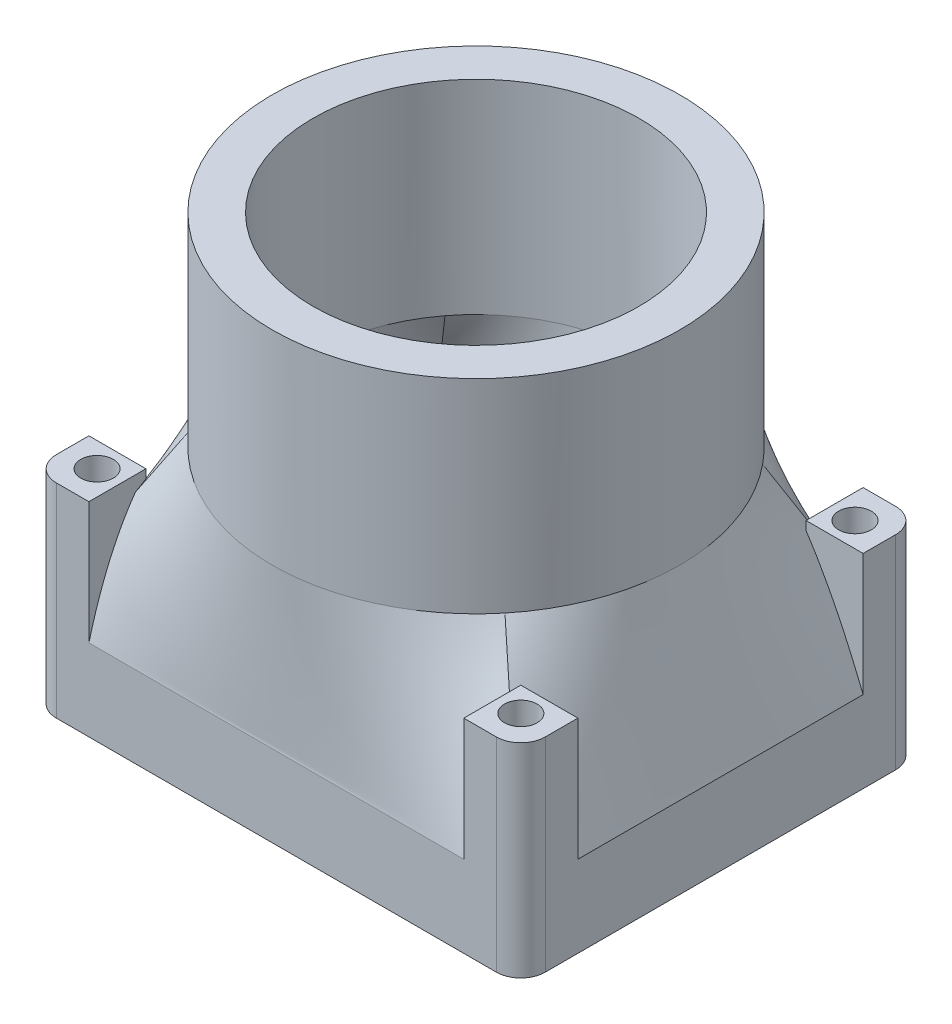
SolidWorks part; units mm, degrees
ref_plane "Front Plane" through (0, 0, 0) normal (0, 0, 1) x (1, 0, 0)
ref_plane "Top Plane" through (0, 0, 0) normal (0, 1, 0) x (1, 0, 0)
ref_plane "Right Plane" through (0, 0, 0) normal (1, 0, 0) x (0, 0, -1)
sketch "Sketch1" plane through (0, 0, 0) normal (0, 1, 0) x (1, 0, 0)
  line L0 (0, 24.5) -> (0, -24.5) construction
  line L1 (-30, -24.5) -> (30, -24.5)
  line L2 (-30, -24.5) -> (-30, 24.5)
  line L3 (-30, 24.5) -> (30, 24.5)
  line L4 (30, -24.5) -> (30, 24.5)
  line L5 (-30, -24.5) -> (30, 24.5) construction
  line L6 (-30, 24.5) -> (30, -24.5) construction
  line L7 (-30, 0) -> (30, 0) construction
  line L9 (-23, -17.5) -> (23, -17.5)
  line L10 (-23, -17.5) -> (-23, 17.5)
  line L11 (-23, 17.5) -> (23, 17.5)
  line L12 (23, -17.5) -> (23, 17.5)
  line L13 (-23, -17.5) -> (23, 17.5) construction
  line L14 (-23, 17.5) -> (23, -17.5) construction
  circle A0 centre (-26, 20.5) radius 2
  circle A1 centre (26, 20.5) radius 2
  circle A2 centre (26, -20.5) radius 2
  circle A3 centre (-26, -20.5) radius 2
  point P0 (0, 0)
  point P18 (0, 0)
  dimension "D1" = 4
  dimension "D2" = 4
  dimension "D3" = 4
  dimension "D4" = 60
  dimension "D5" = 49
  dimension "D6" = 35
  dimension "D7" = 46
extrude "Boss-Extrude1" add sketch "Sketch1" along normal blind 10
sketch "Sketch2" plane through (0, 10, 0) normal (0, 1, 0) x (1, 0, 0)
  line L1 (-23, -17.5) -> (23, -17.5)
  line L2 (-23, -17.5) -> (-23, 17.5)
  line L3 (-23, 17.5) -> (23, 17.5)
  line L4 (23, -17.5) -> (23, 17.5)
  line L5 (-23, -17.5) -> (23, 17.5) construction
  line L6 (-23, 17.5) -> (23, -17.5) construction
  point P0 (0, 0)
ref_plane "Plane2" through (0, 30, 0) normal (0, 1, 0) x (1, 0, 0)
sketch "Sketch8" plane through (0, 30, 0) normal (0, 1, 0) x (1, 0, 0)
  circle A0 centre (0, 0) radius 25
  dimension "D1" = 50
sketch "Sketch9" plane through (0, 10, 0) normal (0, 1, 0) x (1, 0, 0)
  line L1 (30, -24.5) -> (-30, -24.5)
  line L2 (30, -24.5) -> (30, 24.5)
  line L3 (30, 24.5) -> (-30, 24.5)
  line L4 (-30, -24.5) -> (-30, 24.5)
sketch "Sketch3" plane through (0, 30, 0) normal (0, 1, 0) x (1, 0, 0)
  circle A2 centre (0, 0) radius 20
  dimension "D1" = 40
loft "Loft1" add profiles "Sketch9", "Sketch8" connector at (-30, 10, 24.5) connector at (0, 30, 25)
loft "Cut-Loft1" cut profiles "Sketch2", "Sketch3" connector at (-23, 10, 17.5) connector at (0, 30, 20)
sketch "Sketch6" plane through (0, 0, 0) normal (0, -1, 0) x (1, 0, 0)
  circle A0 centre (26, 20.5) radius 2
  circle A1 centre (26, -20.5) radius 2
  circle A2 centre (-26, -20.5) radius 2
  circle A3 centre (-26, 20.5) radius 2
extrude "Cut-Extrude3" cut sketch "Sketch6" against normal through all
sketch "Sketch7" plane through (0, 0, 0) normal (0, -1, 0) x (1, 0, 0)
  line L0 (23, 0) -> (-23, 0) construction
  line L1 (-30, 24.5) -> (-23, 24.5)
  line L2 (-30, 24.5) -> (-30, 17.5)
  line L3 (-30, 17.5) -> (-23, 17.5)
  line L4 (-23, 24.5) -> (-23, 17.5)
  line L5 (23, 17.5) -> (23, -17.5) construction
  line L6 (-23, -17.5) -> (-23, 17.5) construction
  line L7 (0, 17.5) -> (0, -17.5) construction
  line L8 (-23, 17.5) -> (23, 17.5) construction
  line L9 (23, -17.5) -> (-23, -17.5) construction
  line L10 (-30, -17.5) -> (-23, -17.5)
  line L11 (-30, -24.5) -> (-30, -17.5)
  line L12 (-30, -24.5) -> (-23, -24.5)
  line L13 (-23, -24.5) -> (-23, -17.5)
  line L14 (23, -24.5) -> (23, -17.5)
  line L15 (30, -24.5) -> (23, -24.5)
  line L16 (30, -24.5) -> (30, -17.5)
  line L17 (30, -17.5) -> (23, -17.5)
  line L18 (23, 24.5) -> (23, 17.5)
  line L19 (30, 17.5) -> (23, 17.5)
  line L20 (30, 24.5) -> (30, 17.5)
  line L21 (30, 24.5) -> (23, 24.5)
  circle A0 centre (-26, 20.5) radius 2
  circle A1 centre (-26, -20.5) radius 2
  circle A2 centre (26, -20.5) radius 2
  circle A3 centre (26, 20.5) radius 2
extrude "Boss-Extrude4" add sketch "Sketch7" against normal blind 25
sketch "Sketch10" plane through (0, 30, 0) normal (0, 1, 0) x (1, 0, 0)
  circle A0 centre (0, 0) radius 20
  circle A1 centre (0, 0) radius 25
extrude "Boss-Extrude5" add sketch "Sketch10" along normal blind 25
fillet "Fillet2" radius 3 4 edges at (-30, 12.5, 24.5) (-30, 12.5, -24.5) (30, 12.5, -24.5) (30, 12.5, 24.5)
